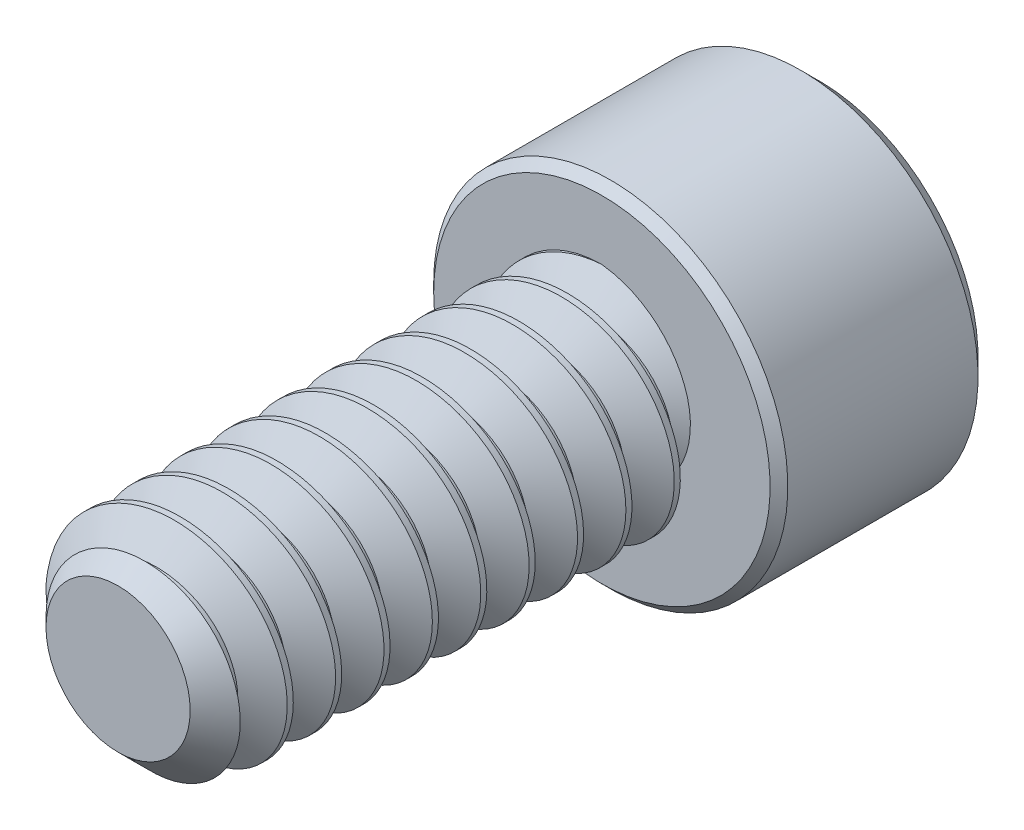
SolidWorks part; units mm, degrees
ref_plane "Front Plane" through (0, 0, 0) normal (0, 0, 1) x (1, 0, 0)
ref_plane "Top Plane" through (0, 0, 0) normal (0, 1, 0) x (1, 0, 0)
ref_plane "Right Plane" through (0, 0, 0) normal (1, 0, 0) x (0, 0, -1)
sketch "Sketch0" plane through (0, 0, 0) normal (1, 0, 0) x (0, 0, -1)
  line L0 (0, 0) -> (6.35, 0) construction
  point P2 (9.1948, 0)
  point P4 (0, 0)
  dimension "D1" = 6.35
  dimension "D2" = 2.8448
  dimension "Min Thread" = 0
sketch "Sketch1" plane through (0, 0, 0) normal (0, 0, 1) x (1, 0, 0)
  circle A0 centre (0, 0) radius 1.4224
  dimension "OD" = 2.8448
extrude "Extrude1" add sketch "Sketch1" against normal blind 6.35
sketch "Sketch2" plane through (0, 0, 0) normal (0, 0, 1) x (1, 0, 0)
  circle A0 centre (0, 0) radius 1.4224 construction
  circle A1 centre (0, 0) radius 1.4224
curve "Helix/Spiral1" pitch 0.635 height 6.985 radius 1.4224 centre (0, 0, 0) axis (0, 0, -1) start towards (0, 1, 0) parameters "pitch"=0.635
chamfer "Chamfer3" distance 0.4763 angle 45 1 edges at (1.4224, 0, 0)
sketch "Sketch3" plane through (0, 0, 0) normal (1, 0, 0) x (0, 0, -1)
  line L0 (-0.5556, 1.4224) -> (-0.3175, 1.01)
  line L1 (-0.3175, 1.01) -> (-0.2381, 1.01)
  line L2 (-0.2381, 1.01) -> (0, 1.4224)
  line L3 (-0.5556, 1.4224) -> (0, 1.4224)
  line L4 (-0.2778, 1.4224) -> (-0.2778, 1.01) construction
  line L5 (-0.4366, 1.2162) -> (-0.1191, 1.2162) construction
  line L6 (0, 1.4224) -> (0, -1.4224) construction
  dimension "D1" = 0.0794
  dimension "D2" = 0.3175
  dimension "D3" = 60
sweep "Cut-Sweep1" cut profiles "Sketch3" path "Helix/Spiral1"
sketch "Sketch5" plane through (0, 0, 0) normal (1, 0, 0) x (0, 0, -1)
  line L0 (6.35, -1.0232) -> (6.35, 1.0149) construction
  line L1 (6.35, 1.4224) -> (0, 1.4224)
  line L2 (6.35, 1.4224) -> (6.35, 0)
  line L3 (6.35, 0) -> (-0.5177, 0)
  line L4 (0, 0) -> (6.35, 0) construction
  line L5 (0, 1.4224) -> (-0.5177, 0)
  line L6 (0, 0) -> (8.89, 0) construction
  dimension "D1" = 70
  dimension "D3" = 2.54
revolve "partially thread" [suppressed] add sketch "Sketch5" angle 360 about L6
sketch "Sketch6" plane through (0, 0, -6.35) normal (0, 0, -1) x (-1, 0, 0)
  circle A0 centre (0, 0) radius 2.3241
  dimension "head dia" = 4.6482
extrude "Extrude2" add sketch "Sketch6" along normal blind 2.8448
sketch "Sketch7" plane through (0, 0, -9.1948) normal (0, 0, -1) x (-1, 0, 0)
  line L1 (0, 1.3748) -> (-1.1906, 0.6874)
  line L2 (-1.1906, 0.6874) -> (-1.1906, -0.6874)
  line L3 (-1.1906, -0.6874) -> (0, -1.3748)
  line L4 (0, -1.3748) -> (1.1906, -0.6874)
  line L5 (1.1906, -0.6874) -> (1.1906, 0.6874)
  line L6 (1.1906, 0.6874) -> (0, 1.3748)
  circle A0 centre (0, 0) radius 1.1906 construction
  dimension "hex dia" = 2.3813
extrude "Cut-Extrude1" cut sketch "Sketch7" against normal blind 1.7859
sketch "Sketch8" plane through (0, 0, -9.1948) normal (0, 0, -1) x (-1, 0, 0)
  circle A0 centre (0, 0) radius 1.3748
extrude "Cut-Extrude2" cut sketch "Sketch8" against normal through all draft 45
chamfer "Chamfer1" distance 0.2324 angle 45 1 edges at (-2.3241, 0, -9.1948)
chamfer "Chamfer2" distance 0.1162 angle 45 1 edges at (-2.3241, 0, -6.35)
sketch "Sketch9" plane through (0, 0, 0) normal (1, 0, 0) x (0, 0, -1)
  line L0 (0, 1.4224) -> (0, -1.4224) construction
  line L1 (1.5875, 1.4224) -> (1.5875, -1.4224) construction
  line L2 (9.1948, 2.3241) -> (9.1948, -2.3241) construction
  line L3 (6.35, 2.3241) -> (6.35, -2.3241) construction
  line L4 (6.35, 2.2079) -> (6.35, -2.2079) construction
  line L5 (9.1948, -2.0917) -> (9.1948, 2.0917) construction
  line L6 (6.35, -2.3241) -> (6.35, 2.3241) construction
  line L7 (0, 0.9462) -> (0, -0.9462) construction
  line L8 (-0.5556, 1.4224) -> (0, 1.4224) construction
  line L9 (1.5875, 0) -> (0, 0) construction
  dimension "D1" = 1.5875
equation "\"D3@Helix/Spiral1\" = \"screw length@Extrude1\"+\"pitch@Helix/Spiral1\""
equation "\"D1@Sketch3\" = \"pitch@Helix/Spiral1\"*.125"
equation "\"D2@Sketch3\" = \"pitch@Helix/Spiral1\"*.5"
equation "\"D1@Cut-Extrude1\" = \"hex dia@Sketch7\"*.75"
equation "\"D1@Chamfer1\" = \"head dia@Sketch6\"*.05"
equation "\"D1@Sketch9\" = \"pitch@Helix/Spiral1\"*2.50"
equation "\"D1@Chamfer2\" = \"D1@Chamfer1\"/2"
equation "\"D1@Chamfer3\" = \"pitch@Helix/Spiral1\"*.750"
equation "\"D1@Sketch0\" = \"screw length@Extrude1\""
equation "\"D2@Sketch0\" = \"head depth@Extrude2\""
